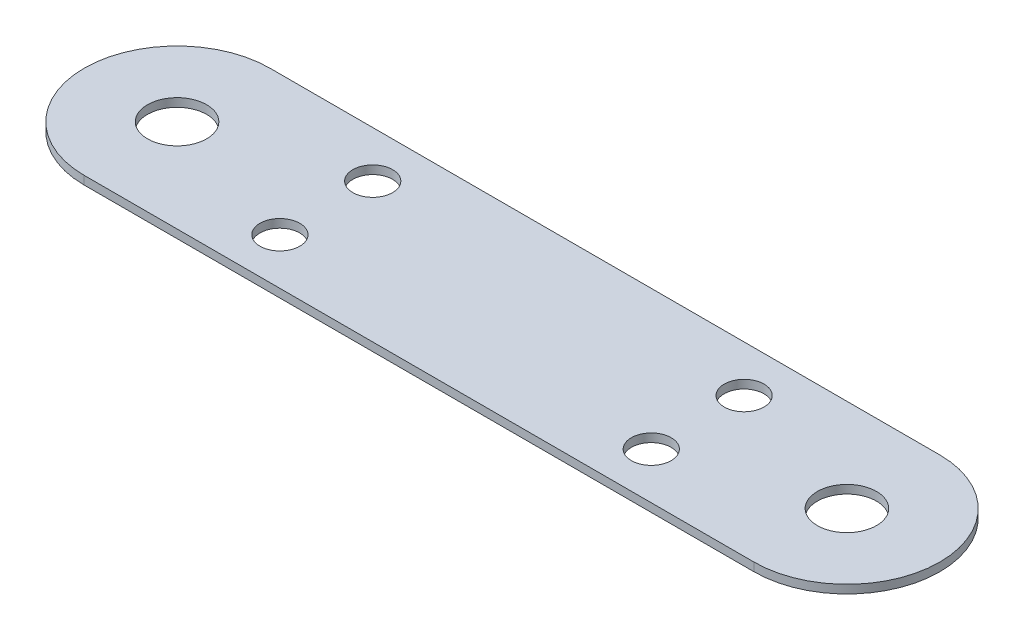
SolidWorks part; units mm, degrees
ref_plane "Front Plane" through (0, 0, 0) normal (0, 0, 1) x (1, 0, 0)
ref_plane "Top Plane" through (0, 0, 0) normal (0, 1, 0) x (1, 0, 0)
ref_plane "Right Plane" through (0, 0, 0) normal (1, 0, 0) x (0, 0, -1)
sketch "Sketch1" plane through (0, 0, 0) normal (0, 1, 0) x (1, 0, 0)
  line L0 (126.2582, 0) -> (-126.2582, 0)
  line L1 (-126.2582, 35) -> (126.2582, 35)
  line L3 (-126.2582, -35) -> (126.2582, -35)
  line L4 (-70, 35) -> (-70, 0) construction
  line L5 (-70, 0) -> (-70, -35) construction
  line L6 (70, 35) -> (70, 0) construction
  line L7 (70, 0) -> (70, -35) construction
  circle A0 centre (-126.2582, 0) radius 35
  circle A1 centre (126.2582, 0) radius 35
  circle A2 centre (-126.2582, 0) radius 11.15
  circle A3 centre (126.2582, 0) radius 11.15
  circle A5 centre (-70, -17.5) radius 7.5
  circle A6 centre (-70, 17.5) radius 7.5
  circle A7 centre (70, 17.5) radius 7.5
  circle A8 centre (70, -17.5) radius 7.5
  point P4 (0, 0)
  dimension "D1" = 22.3
  dimension "D3" = 70
  dimension "D4" = 15
  dimension "D5" = 70
  dimension "D6" = 70
extrude "Boss-Extrude1" add sketch "Sketch1" along normal blind 3.175 contours A2 A0 | L0 A0 L3 A1 | L0 A1 L1 A0 | A3 A1 region at (0, 0, -18.276) region at (-102.2095, 0, 24.0487) region at (0, 0, 18.276) region at (102.2095, 0, -24.0487)
